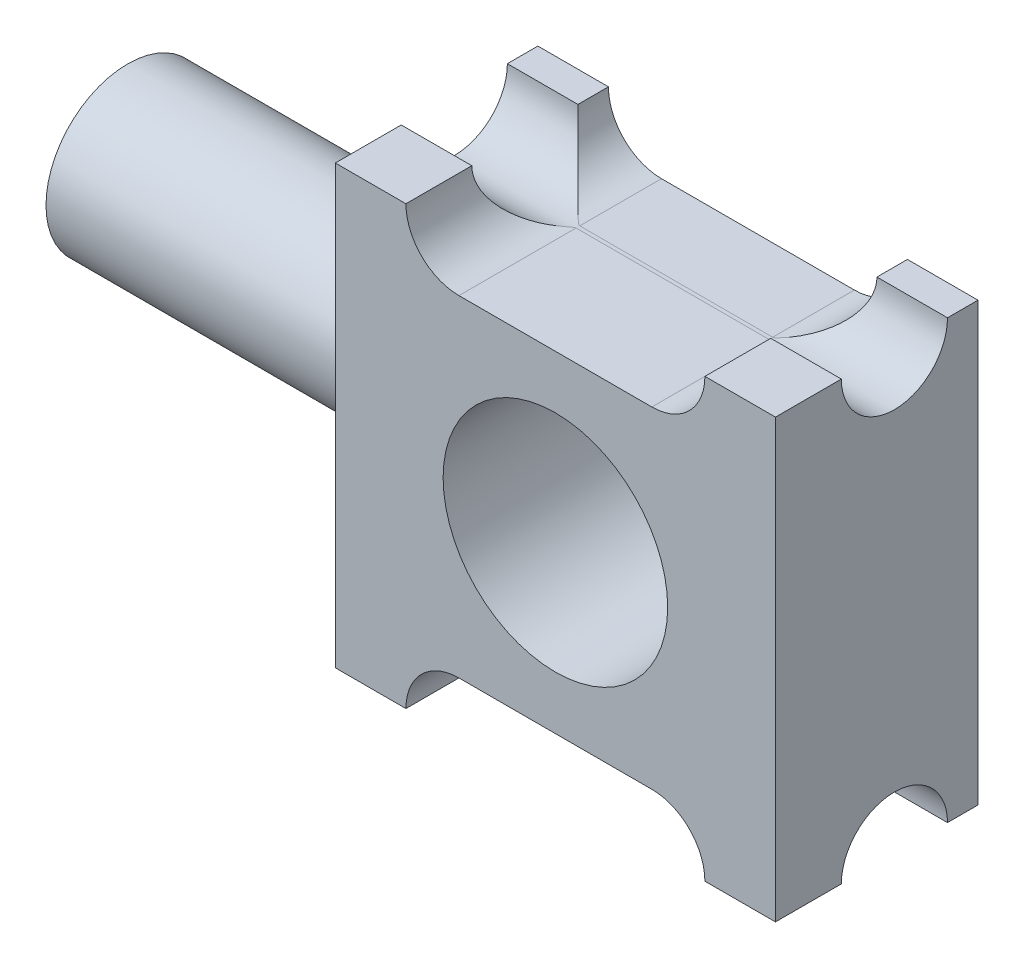
SolidWorks part; units mm, degrees
ref_plane "Front Plane" through (0, 0, 0) normal (0, 0, 1) x (1, 0, 0)
ref_plane "Top Plane" through (0, 0, 0) normal (0, 1, 0) x (1, 0, 0)
ref_plane "Right Plane" through (0, 0, 0) normal (1, 0, 0) x (0, 0, -1)
sketch "Sketch1" plane through (0, 0, 0) normal (0, 0, 1) x (1, 0, 0)
  line L1 (-6.8453, 6.8) -> (6.8453, 6.8)
  line L2 (-6.8453, 6.8) -> (-6.8453, -6.8)
  line L3 (-6.8453, -6.8) -> (6.8453, -6.8)
  line L4 (6.8453, 6.8) -> (6.8453, -6.8)
  line L5 (-6.8453, 6.8) -> (6.8453, -6.8) construction
  line L6 (-6.8453, -6.8) -> (6.8453, 6.8) construction
  point P0 (0, 0)
  dimension "D1" = 13.6906
  dimension "D2" = 13.6
extrude "Boss-Extrude1" add sketch "Sketch1" along normal blind 6.3
sketch "Sketch2" plane through (6.8453, 0, 0) normal (1, 0, 0) x (0, 0, -1)
  line L0 (-6.3, 6.8) -> (0, 6.8) construction
  line L1 (0, -6.8) -> (0, 6.8) construction
  line L2 (-6.3, 0) -> (0, 0) construction
  line L3 (-6.3, -6.8) -> (-6.3, 6.8) construction
  circle A0 centre (-2.6, 6.8) radius 1.651
  circle A1 centre (-2.6, -6.8) radius 1.651
  dimension "D2" = 3.302
  dimension "D1" = 2.6
extrude "Cut-Extrude1" cut sketch "Sketch2" against normal through all
sketch "Sketch3" plane through (0, 0, 6.3) normal (0, 0, 1) x (1, 0, 0)
  line L0 (6.8453, 6.8) -> (-6.8453, 6.8) construction
  line L1 (-3, 6.8) -> (3, 6.8)
  line L2 (-3, 6.8) -> (-3, 5.15)
  line L3 (-3, 5.15) -> (3, 5.15)
  line L4 (3, 6.8) -> (3, 5.15)
  line L5 (0, 5.15) -> (0, 7.1831) construction
  line L6 (-6.8453, 0) -> (0, 5.15) construction
  line L7 (-6.8453, 6.8) -> (-6.8453, -6.8) construction
  line L8 (0, 5.15) -> (6.8453, 0) construction
  line L9 (6.8453, -6.8) -> (6.8453, 6.8) construction
  line L10 (-6.8453, 0) -> (6.8453, 0) construction
  line L11 (0, -5.15) -> (6.8453, 0) construction
  line L12 (-6.8453, 0) -> (0, -5.15) construction
  line L13 (0, -5.15) -> (0, -7.1831) construction
  line L14 (3, -6.8) -> (3, -5.15)
  line L15 (-3, -5.15) -> (3, -5.15)
  line L16 (-3, -6.8) -> (-3, -5.15)
  line L17 (-3, -6.8) -> (3, -6.8)
  line L18 (-4.65, 6.8) -> (4.65, 6.8)
  line L19 (-3, -6.8) -> (3, -6.8)
  arc A0 (3, 5.15) -> (4.65, 6.8) centre (3, 6.8) ccw
  arc A1 (-3, 5.15) -> (-4.65, 6.8) centre (-3, 6.8) cw
  arc A2 (-3, -5.15) -> (-4.65, -6.8) centre (-3, -6.8) ccw
  arc A3 (3, -5.15) -> (4.65, -6.8) centre (3, -6.8) cw
  line M9 (6.8453, 6.8) -> (-6.8453, 6.8)
  line M11 (-6.8453, -6.8) -> (6.8453, -6.8)
  dimension "D2" = 1.65
  dimension "D1" = 1.65
  dimension "D3" = 6
extrude "Cut-Extrude2" cut sketch "Sketch3" against normal through all contours A1 L2 M9 | L4 L2 L3 M9 | L4 A0 M9 | A3 L14 M11 | L16 L14 L15 M11 | L16 A2 M11 region at (0, 5.975, 6.3) region at (-3.7003, 6.0997, 6.3) region at (3.7003, 6.0997, 6.3) region at (0, -5.975, 6.3) region at (3.7003, -6.0997, 6.3) region at (-3.7003, -6.0997, 6.3)
sketch "Sketch4" plane through (0, 0, 6.3) normal (0, 0, 1) x (1, 0, 0)
  circle A0 centre (0, 0) radius 3.4925
  dimension "D1" = 6.985
extrude "Cut-Extrude3" cut sketch "Sketch4" against normal through all
sketch "Sketch5" plane through (-6.8453, 0, 0) normal (-1, 0, 0) x (0, 0, 1)
  line L0 (2.6, 5.149) -> (2.6, -5.149) construction
  circle A0 centre (2.6, 0) radius 2.54
  arc A2 (0.949, 6.8) -> (4.251, 6.8) centre (2.6, 6.8) ccw construction
  arc A3 (4.251, -6.8) -> (0.949, -6.8) centre (2.6, -6.8) ccw construction
  dimension "D1" = 5.08
extrude "Boss-Extrude2" add sketch "Sketch5" along normal blind 10.16
